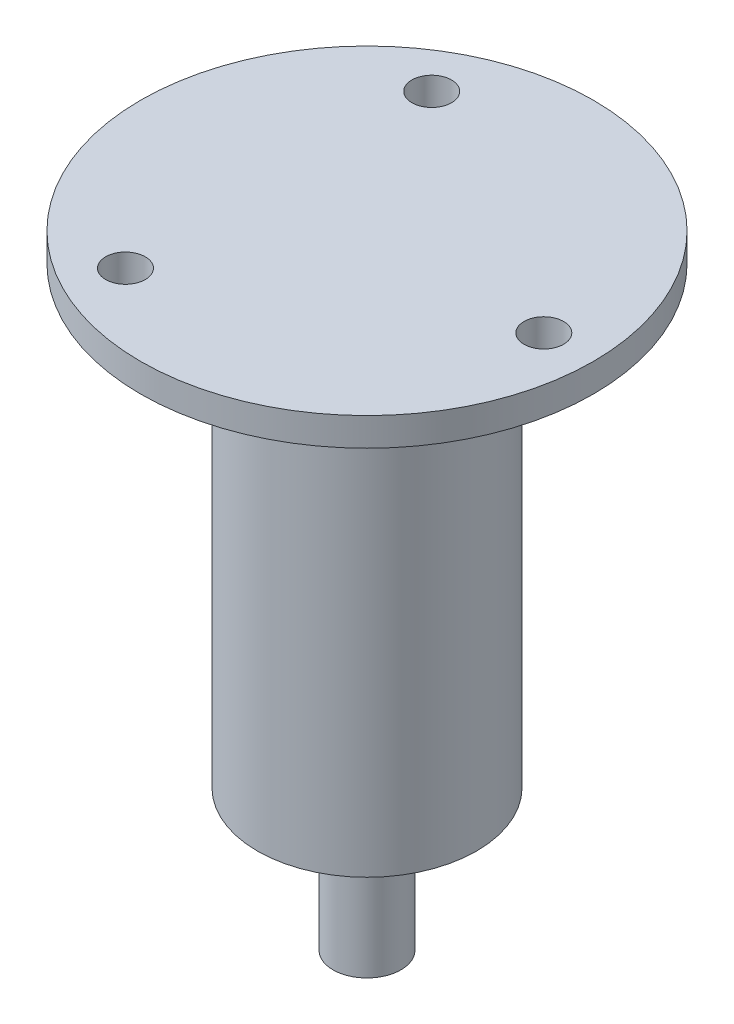
SolidWorks part; units mm, degrees
ref_plane "Front Plane" through (0, 0, 0) normal (0, 0, 1) x (1, 0, 0)
ref_plane "Top Plane" through (0, 0, 0) normal (0, 1, 0) x (1, 0, 0)
ref_plane "Right Plane" through (0, 0, 0) normal (1, 0, 0) x (0, 0, -1)
sketch "Sketch1" plane through (0, 0, 0) normal (1, 0, 0) x (0, 0, -1)
  line L0 (0, 23.9311) -> (0, -15.9842) construction
  line L1 (0, 20.05) -> (2.95, 20.05)
  line L2 (2.95, 20.05) -> (2.95, 14.05)
  line L3 (2.95, 14.05) -> (16, 14.05)
  line L4 (16, 14.05) -> (16, 12.05)
  line L5 (16, 12.05) -> (7.75, 12.05)
  line L6 (7.75, 12.05) -> (7.75, -20.05)
  line L7 (7.75, -20.05) -> (0, -20.05)
  line L8 (0, -20.05) -> (0, 20.05)
  dimension "D1" = 5.9
  dimension "D2" = 34.1
  dimension "D3" = 2
  dimension "D4" = 6
  dimension "D5" = 32
  dimension "D6" = 15.5
revolve "Revolve1" add sketch "Sketch1" angle 360 about L0
sketch "Sketch2" plane through (0, 14.05, 0) normal (0, 1, 0) x (1, 0, 0)
  circle A0 centre (0, 0) radius 12.5 construction
  circle A1 centre (12.5, 0) radius 1.4
  circle A2 centre (-6.25, -10.8253) radius 1.4
  circle A3 centre (-6.25, 10.8253) radius 1.4
  point P11 (0, 0)
  dimension "D1" = 3
  dimension "D2" = 25
  dimension "D3" = 2.8
extrude "Cut-Extrude1" cut sketch "Sketch2" against normal through all both
sketch "Sketch3" plane through (0, 0, 0) normal (0, 1, 0) x (1, 0, 0)
  circle A0 centre (0, 0) radius 2.4
  dimension "D1" = 4.8
extrude "Boss-Extrude1" [suppressed] add sketch "Sketch3" along normal mid plane 100
split "Split1" [suppressed] bodies to split 103
sketch "Sketch4" plane through (0, 0, 0) normal (0, 1, 0) x (1, 0, 0)
  circle A0 centre (0, 0) radius 2.4
  dimension "D1" = 4.8
sketch "Sketch5" plane through (0, 0, 0) normal (1, 0, 0) x (0, 0, -1)
  line L0 (0, 0) -> (0, 20.05)
  line L1 (2.4, 0) -> (-2.4, 0) construction
  line L2 (2.95, 20.05) -> (-2.95, 20.05) construction
  line L3 (6, 26.05) -> (24, 26.05)
  line L4 (30, 32.05) -> (30, 52.05)
  line L5 (0, 0) -> (0, -30)
  arc A0 (0, 20.05) -> (6, 26.05) centre (6, 20.05) cw
  arc A1 (24, 26.05) -> (30, 32.05) centre (24, 32.05) ccw
  dimension "D1" = 6
  dimension "D2" = 20
  dimension "D3" = 30
  dimension "D4" = 30
sweep "Sweep1" add profiles "Sketch4" path "Sketch5"
split "Split2" bodies to split 106 resulting bodies 107 108 split by face at (12.5, 14.05, 1.4)
delete or keep bodies "Body-Delete/Keep 1" [suppressed] type delete bodies bodies 108
delete or keep bodies "Body-Delete/Keep 2" type delete bodies bodies 107
